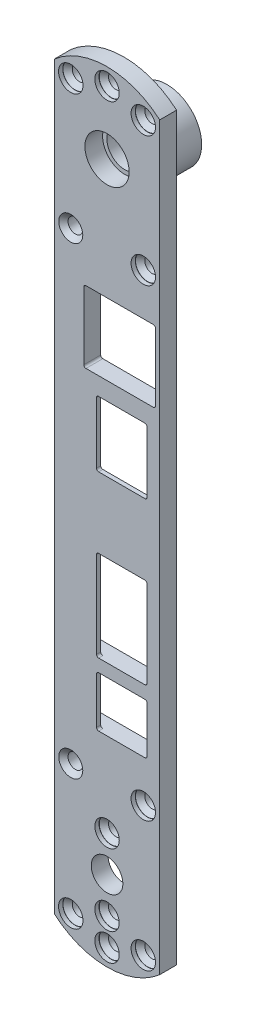
SolidWorks part; units mm, degrees
ref_plane "Front Plane" through (0, 0, 0) normal (0, 0, 1) x (1, 0, 0)
ref_plane "Top Plane" through (0, 0, 0) normal (0, 1, 0) x (1, 0, 0)
ref_plane "Right Plane" through (0, 0, 0) normal (1, 0, 0) x (0, 0, -1)
sketch "Sketch1" plane through (0, 0, 0) normal (0, 0, 1) x (1, 0, 0)
  line L0 (18.375, 147) -> (18.375, 0)
  line L1 (43.375, 147) -> (43.375, 0)
  circle A0 centre (30.875, 8.5) radius 1.75
  circle A1 centre (30.875, 0) radius 12.5 construction
  circle A2 centre (30.875, 0) radius 12.5
  circle A3 centre (30.875, -8.5) radius 1.75
  circle A4 centre (30.875, 0) radius 3.75
  circle A5 centre (30.875, -8.5) radius 1.25 construction
  circle A6 centre (30.875, 147) radius 12.5
  circle A7 centre (30.875, 147) radius 5.25
  circle A8 centre (30.875, 147) radius 5 construction
  circle A11 centre (30.875, 8.5) radius 1.25 construction
  circle A12 centre (30.875, 147) radius 5 construction
  dimension "D2" = 3.5
  dimension "D3" = 7.5
  dimension "D1" = 0.25
extrude "Boss-Extrude1" add sketch "Sketch1" along normal blind 4 contours A6 | A6 L0 A2 L1 | A2 A4 A3 A0 region at (30.875, 73.5, 0) region at (30.875, 159.1464, 0) region at (30.875, 12.1464, 0)
sketch "Sketch2" plane through (0, 0, 0) normal (0, 0, 1) x (1, 0, 0)
  circle A0 centre (30.875, 147) radius 5.25
  circle A1 centre (30.875, 147) radius 5.25 construction
  circle A2 centre (30.875, 147) radius 8.25
  dimension "D1" = 3
extrude "Boss-Extrude2" add sketch "Sketch2" against normal blind 0.2
sketch "Sketch3" plane through (0, 0, -0.2) normal (0, 0, -1) x (-1, 0, 0)
  circle A0 centre (-30.875, 147) radius 8.25 construction
  circle A1 centre (-30.875, 147) radius 8.25
  circle A2 centre (-30.875, 147) radius 4.25
  circle A3 centre (-30.875, 147) radius 5.25 construction
  dimension "D1" = 1
extrude "Boss-Extrude3" add sketch "Sketch3" along normal blind 5.8
sketch "Sketch4" plane through (0, 0, -6) normal (0, 0, -1) x (-1, 0, 0)
  circle A0 centre (-30.875, 147) radius 8.25 construction
  circle A1 centre (-30.875, 147) radius 8.25
  circle A2 centre (-30.875, 147) radius 5.25
  circle A3 centre (-30.875, 147) radius 5.25 construction
extrude "Boss-Extrude4" add sketch "Sketch4" along normal blind 4.2
sketch "Sketch9" plane through (0, 0, 0) normal (0, 0, -1) x (-1, 0, 0)
  line L0 (-43.375, 161.3091) -> (-43.375, -14.3091)
  line L1 (-43.375, 147) -> (-43.375, 0) construction
  line L2 (-18.375, 161.3091) -> (-18.375, -14.3091)
  line L3 (-18.375, 147) -> (-18.375, 0) construction
  circle A0 centre (-30.875, 147) radius 19
  circle A1 centre (-30.875, 0) radius 19
  arc A2 (-18.375, 147) -> (-43.375, 147) centre (-30.875, 147) ccw construction
  arc M15 (-18.375, 147) -> (-43.375, 147) centre (-30.875, 147) ccw
  arc M17 (-43.375, 0) -> (-18.375, 0) centre (-30.875, 0) ccw
  dimension "D1" = 6.5
extrude "Boss-Extrude5" add sketch "Sketch9" against normal up to surface (4 mm away) contours L2 A0 L0 M15 | L0 A1 L2 M17 region at (30.875, 160.2864, 0) region at (30.875, -13.2864, 0) up to face at (36.125, 147, 4)
sketch "Sketch10" plane through (0, 0, 4) normal (0, 0, 1) x (1, 0, 0)
  line L0 (30.875, 166) -> (30.875, -19) construction
  line L1 (30.875, 147) -> (19.977, 162.5639) construction
  line L2 (39.4786, 159.2873) -> (39.4786, -12.2873) construction
  line L3 (18.375, 73.5) -> (43.375, 73.5) construction
  line L4 (18.375, 161.3091) -> (18.375, -14.3091) construction
  line L5 (43.375, 161.3091) -> (43.375, -14.3091) construction
  circle A0 centre (30.875, 147) radius 15
  arc A1 (43.375, 161.3091) -> (18.375, 161.3091) centre (30.875, 147) ccw construction
  arc A2 (18.375, -14.3091) -> (43.375, -14.3091) centre (30.875, 0) ccw construction
  circle A3 centre (30.875, 162) radius 1.75
  circle A4 centre (22.2714, 159.2873) radius 1.75
  circle A5 centre (39.4786, 159.2873) radius 1.75
  circle A6 centre (39.4786, -12.2873) radius 1.75
  circle A7 centre (30.875, -15) radius 1.75
  circle A8 centre (22.2714, -12.2873) radius 1.75
  circle A9 centre (39.4786, 128.5) radius 1.75
  circle A10 centre (39.4786, 18.5) radius 1.75
  circle A11 centre (22.2714, 18.5) radius 1.75
  circle A12 centre (22.2714, 128.5) radius 1.75
  dimension "D1" = 4
  dimension "D2" = 3.5
  dimension "D3" = 35
  dimension "D4" = 110
extrude "Cut-Extrude4" cut sketch "Sketch10" against normal up to next contours A0 A4 | A0 A4 | A0 A3 | A0 A3 | A5 A0 | A5 A0 | A8 | A7 | A6 | A9 | A10 | A12 | A11 region at (39.0423, 158.6641, 4) region at (39.8939, 159.8804, 4) region at (21.8561, 159.8804, 4) region at (22.7077, 158.6641, 4) region at (30.875, 161.2392, 4) region at (30.875, 162.724, 4) region at (39.4786, -12.2873, 4) region at (30.875, -15, 4) region at (22.2714, -12.2873, 4) region at (39.4786, 128.5, 4) region at (39.4786, 18.5, 4) region at (22.2714, 18.5, 4) region at (22.2714, 128.5, 4)
sketch "Sketch8" plane through (0, 0, 4) normal (0, 0, 1) x (1, 0, 0)
  circle A0 centre (30.875, 8.5) radius 2.9
  circle A1 centre (30.875, -8.5) radius 2.9
  circle A2 centre (22.2714, -12.2873) radius 2.9
  circle A3 centre (30.875, -15) radius 2.9
  circle A4 centre (39.4786, -12.2873) radius 2.9
  circle A5 centre (22.2714, 159.2873) radius 2.9
  circle A6 centre (30.875, 162) radius 2.9
  circle A7 centre (39.4786, 159.2873) radius 2.9
  circle A8 centre (39.4786, 159.2873) radius 1.75 construction
  circle A9 centre (39.4786, -12.2873) radius 1.75 construction
  circle A10 centre (22.2714, -12.2873) radius 1.75 construction
  circle A11 centre (30.875, -15) radius 1.75 construction
  circle A12 centre (39.4786, 128.5) radius 2.9
  circle A13 centre (39.4786, 18.5) radius 2.9
  circle M10 centre (30.875, -8.5) radius 1.75
  circle M11 centre (30.875, 8.5) radius 1.75
  circle M59 centre (39.4786, 18.5) radius 1.75
  circle M60 centre (39.4786, 128.5) radius 1.75
  dimension "D1" = 5.8
extrude "Cut-Extrude3" cut sketch "Sketch8" against normal blind 1 contours A5 | A6 | A7 | A2 | A3 | A4 | A0 M11 | A1 M10 | A12 M60 | A13 M59 region at (28.057, 8.5, 4) region at (28.057, -8.5, 4) region at (22.2714, -12.2873, 4) region at (30.875, -15, 4) region at (39.4786, -12.2873, 4) region at (22.2714, 159.2873, 4) region at (30.875, 162, 4) region at (39.4786, 159.2873, 4) region at (36.6607, 128.5, 4) region at (36.6607, 18.5, 4)
chamfer "Chamfer1" distance 1.1 angle 45 12 edges at (41.2286, -12.2873, 3) (32.625, -15, 3) (24.0214, -12.2873, 3) (41.2286, 159.2873, 3) (32.625, 162, 3) (24.0214, 159.2873, 3) (32.625, -8.5, 3) (32.625, 8.5, 3) (41.2286, 18.5, 3) (41.2286, 128.5, 3) (24.0214, 128.5, 4) (24.0214, 18.5, 4)
fillet "Fillet2" radius 2 1 edges at (39.125, 147, 0)
sketch "Sketch11" plane through (0, 0, 0) normal (0, 0, 1) x (1, 0, 0)
  line L0 (43.375, 161.3091) -> (43.375, -14.3091) construction
  line L1 (25.375, 28.5) -> (43.375, 28.5)
  line L2 (25.375, 28.5) -> (25.375, 118.5)
  line L3 (25.375, 118.5) -> (43.375, 118.5)
  line L4 (43.375, 28.5) -> (43.375, 118.5)
  line L5 (18.375, 73.5) -> (43.375, 73.5) construction
  line L6 (18.375, 161.3091) -> (18.375, -14.3091) construction
  line L7 (25.375, 73.5) -> (43.375, 73.5) construction
  dimension "D2" = 90
  dimension "D3" = 18
extrude "Cut-Extrude5" cut sketch "Sketch11" along normal offset from surface (3 mm away) 1 up to face at (25.1214, 128.5, 4)
sketch "Sketch12" plane through (0, 0, 4) normal (0, 0, 1) x (1, 0, 0)
  line L0 (43.375, 118.5) -> (25.375, 118.5) construction
  line L1 (25.375, 118.5) -> (42.375, 118.5)
  line L2 (25.375, 118.5) -> (25.375, 101.5)
  line L3 (25.375, 101.5) -> (42.375, 101.5)
  line L4 (42.375, 118.5) -> (42.375, 101.5)
  line L5 (25.375, 118.5) -> (25.375, 28.5) construction
  line L6 (25.375, -18.1865) -> (25.375, 165.1865) construction
  line L7 (25.375, 73.5) -> (43.375, 73.5) construction
  line L8 (43.375, 161.3091) -> (43.375, -14.3091) construction
  line L9 (34.375, 165.6748) -> (34.375, -18.6748) construction
  line L10 (18.375, 28.5) -> (43.375, 28.5) construction
  line L11 (28.375, 97.25) -> (40.375, 97.25)
  line L12 (28.375, 97.25) -> (28.375, 81.75)
  line L13 (28.375, 81.75) -> (40.375, 81.75)
  line L14 (40.375, 97.25) -> (40.375, 81.75)
  line L15 (28.375, 97.25) -> (40.375, 81.75) construction
  line L16 (28.375, 81.75) -> (40.375, 97.25) construction
  line L17 (28.375, 65) -> (40.375, 65)
  line L18 (28.375, 65) -> (28.375, 43.5)
  line L19 (28.375, 43.5) -> (40.375, 43.5)
  line L20 (40.375, 65) -> (40.375, 43.5)
  line L21 (18.375, 161.3091) -> (18.375, -14.3091) construction
  line L22 (25.375, 28.5) -> (43.375, 28.5) construction
  line L24 (28.375, 28.5) -> (40.375, 28.5)
  line L25 (28.375, 28.5) -> (28.375, 40.5)
  line L26 (28.375, 40.5) -> (40.375, 40.5)
  line L27 (40.375, 28.5) -> (40.375, 40.5)
  arc A0 (18.375, -14.3091) -> (43.375, -14.3091) centre (30.875, 0) ccw construction
  arc A1 (43.375, 161.3091) -> (18.375, 161.3091) centre (30.875, 147) ccw construction
  point P22 (34.375, 73.5)
  point P23 (34.375, 89.5)
  point P42 (28.375, 34.5)
  dimension "D1" = 17
  dimension "D2" = 17
  dimension "D3" = 29
  dimension "D4" = 15.5
  dimension "D5" = 12
  dimension "D8" = 15
  dimension "D9" = 21.5
  dimension "D10" = 12
extrude "Cut-Extrude6" cut sketch "Sketch12" against normal up to next
sketch "Sketch13" plane through (0, 0, 3) normal (0, 0, -1) x (-1, 0, 0)
  line L0 (-25.375, 101.5) -> (-25.375, 28.5) construction
  line L1 (-25.375, 43.5) -> (-43.375, 43.5)
  line L2 (-25.375, 43.5) -> (-25.375, 40.5)
  line L3 (-25.375, 40.5) -> (-43.375, 40.5)
  line L4 (-43.375, 43.5) -> (-43.375, 40.5)
  line L5 (-43.375, 28.5) -> (-43.375, 118.5) construction
  line L6 (-40.375, 43.5) -> (-28.375, 43.5) construction
  line L7 (-28.375, 40.5) -> (-40.375, 40.5) construction
  line L8 (-28.375, 65) -> (-40.375, 65) construction
  line L9 (-25.375, 68) -> (-43.375, 68)
  line L10 (-25.375, 68) -> (-25.375, 65)
  line L11 (-25.375, 65) -> (-43.375, 65)
  line L12 (-43.375, 68) -> (-43.375, 65)
  line L13 (-34.375, 68) -> (-34.375, 65) construction
  line L14 (-34.375, 43.5) -> (-34.375, 40.5) construction
  line L15 (-28.375, 97.25) -> (-40.375, 97.25) construction
  line L16 (-25.375, 101.5) -> (-43.375, 101.5)
  line L17 (-25.375, 101.5) -> (-25.375, 97.25)
  line L18 (-25.375, 97.25) -> (-43.375, 97.25)
  line L19 (-43.375, 101.5) -> (-43.375, 97.25)
  line L20 (-40.375, 65) -> (-40.375, 43.5) construction
  line L21 (-43.375, 101.5) -> (-40.375, 101.5)
  line L22 (-43.375, 101.5) -> (-43.375, 40.5)
  line L23 (-43.375, 40.5) -> (-40.375, 40.5)
  line L24 (-40.375, 101.5) -> (-40.375, 40.5)
  line L26 (-42.375, 118.5) -> (-43.375, 118.5)
  line L27 (-42.375, 118.5) -> (-42.375, 28.5)
  line L28 (-42.375, 28.5) -> (-43.375, 28.5)
  line L29 (-43.375, 118.5) -> (-43.375, 28.5)
  line M11 (-40.375, 97.25) -> (-28.375, 97.25)
  line M13 (-40.375, 65) -> (-28.375, 65)
  line M15 (-28.375, 43.5) -> (-40.375, 43.5)
  line M17 (-40.375, 40.5) -> (-28.375, 40.5)
  line M20 (-25.375, 28.5) -> (-25.375, 101.5)
  line M21 (-25.375, 101.5) -> (-42.375, 101.5)
  line M22 (-42.375, 101.5) -> (-42.375, 118.5)
  line M23 (-42.375, 118.5) -> (-43.375, 118.5)
  line M24 (-43.375, 118.5) -> (-43.375, 28.5)
  line M25 (-43.375, 28.5) -> (-40.375, 28.5)
extrude "Boss-Extrude6" add sketch "Sketch13" along normal up to surface (3 mm away) contours L16 L27 L18 L24 | L24 L18 M21 M11 M20 | L9 L24 L11 M13 M20 | L16 M22 M23 M24 | L27 L16 L18 M24 | L27 L18 L9 M24 | L27 L9 L11 M24 | L27 L11 L1 M24 | L9 L27 L11 L24 | L27 L23 M24 M25 | L27 L1 L23 M24 | L1 L27 L3 L24 | L24 L3 L1 M15 M17 M20 region at (32.875, 42, 3) region at (32.875, 66.5, 3) region at (41.375, 42, 3) region at (42.875, 42, 3) region at (42.875, 54.25, 3) region at (41.375, 66.5, 3) region at (32.875, 99.375, 3) region at (42.875, 66.5, 3) region at (42.875, 34.5, 3) region at (42.875, 82.625, 3) region at (41.375, 99.375, 3) region at (42.875, 99.375, 3) region at (42.875, 110, 3) up to face at (41.2286, 18.5, 0)
fillet "Fillet3" radius 0.5 16 edges at (40.375, 28.5, 3.5) (40.375, 40.5, 3.5) (28.375, 40.5, 3.5) (28.375, 28.5, 3.5) (28.375, 43.5, 3.5) (28.375, 65, 3.5) (40.375, 65, 3.5) (40.375, 43.5, 3.5) (42.375, 101.5, 2) (25.375, 101.5, 2) (25.375, 118.5, 2) (28.375, 97.25, 3.5) (28.375, 81.75, 3.5) (40.375, 81.75, 3.5) (42.375, 118.5, 2) (40.375, 97.25, 3.5)
